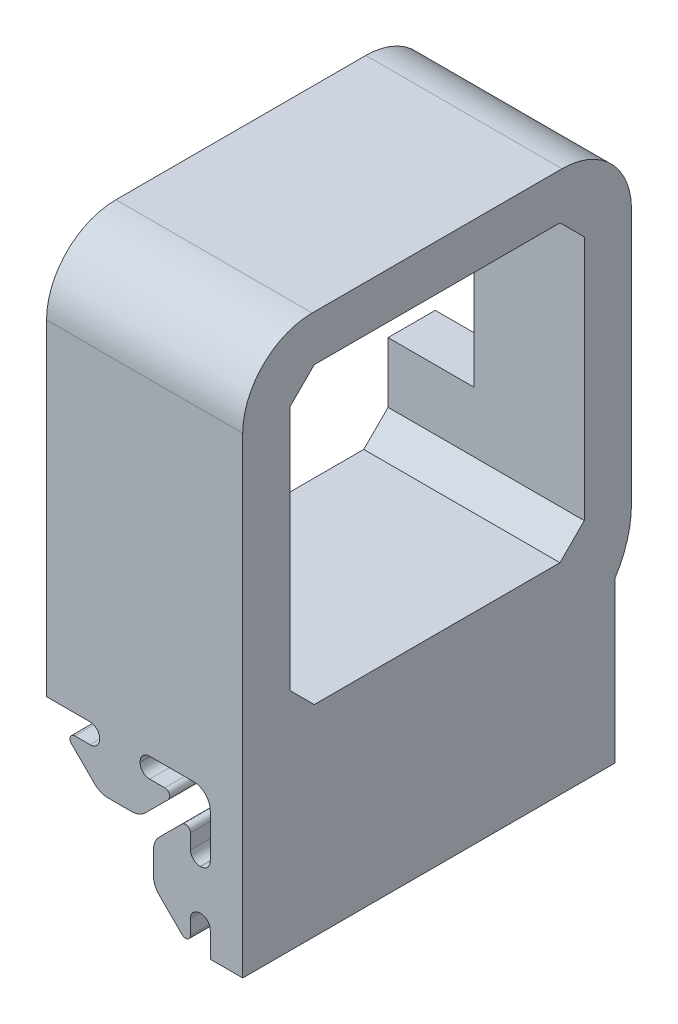
SolidWorks part; units mm, degrees
ref_plane "Front Plane" through (0, 0, 0) normal (0, 0, 1) x (1, 0, 0)
ref_plane "Top Plane" through (0, 0, 0) normal (0, 1, 0) x (1, 0, 0)
ref_plane "Right Plane" through (0, 0, 0) normal (1, 0, 0) x (0, 0, -1)
sketch "Sketch1" plane through (0, 0, 0) normal (0, 0, 1) x (1, 0, 0)
  line L0 (13.02, -7.9417) -> (17.7, -7.9417)
  line L1 (-10.5664, 13.02) -> (-10.5664, 70.02)
  line L2 (-10.5664, 70.02) -> (17.7, 70.02)
  line L3 (17.7, -7.9417) -> (17.7, 70.02)
  line L10 (12.7, -6.3331) -> (12.7, -7.9417) construction
  line L11 (13.02, -5.3171) -> (13.02, -4.2875)
  line L12 (11.651, -2.9185) -> (11.5392, -2.9185)
  line L13 (10.1702, -4.2875) -> (10.1702, -6.4021)
  line L14 (8.9631, -6.9029) -> (5.667, -3.6143)
  line L15 (4.8285, -1.5932) -> (4.8285, 1.5932)
  line L16 (5.667, 3.6143) -> (8.9631, 6.9029)
  line L17 (10.1702, 6.4021) -> (10.1702, 4.2875)
  line L18 (11.5392, 2.9185) -> (11.651, 2.9185)
  line L19 (13.02, 10.5773) -> (13.02, 4.2875)
  line L20 (6.3329, 13.02) -> (10.5626, 13.0198)
  line L22 (6.3329, 13.02) -> (4.2875, 13.02)
  line L23 (2.9185, 11.651) -> (2.9185, 11.5392)
  line L24 (4.2875, 10.1702) -> (6.4768, 10.1702)
  line L25 (6.981, 8.9509) -> (3.6723, 5.6497)
  line L26 (1.6558, 4.8158) -> (-1.6558, 4.8158)
  line L27 (-3.6723, 5.6497) -> (-6.981, 8.9509)
  line L28 (-6.4768, 10.1702) -> (-4.2875, 10.1702)
  line L29 (-2.9185, 11.5392) -> (-2.9185, 11.651)
  line L30 (-4.2875, 13.02) -> (-5.3171, 13.02)
  line L31 (-5.3171, 13.02) -> (-10.5664, 13.02)
  line L32 (13.02, -5.3171) -> (13.02, -7.9417)
  line L33 (13.02, -6.3331) -> (13.02, -7.9417) construction
  line L34 (13.02, 4.2875) -> (13.02, 5.3171) construction
  line L37 (5.3171, 13.02) -> (4.2875, 13.02) construction
  line L38 (-6.3331, 13.02) -> (-9.5504, 13.02) construction
  line L96 (12.7, -5.3171) -> (12.7, -4.2875) construction
  line L97 (11.651, -3.2385) -> (11.5392, -3.2385) construction
  line L98 (10.4902, -4.2875) -> (10.4902, -6.4021) construction
  line L99 (8.7371, -7.1294) -> (5.441, -3.8408) construction
  line L100 (4.5085, -1.5932) -> (4.5085, 1.5932) construction
  line L101 (5.441, 3.8408) -> (8.7371, 7.1294) construction
  line L102 (10.4902, 6.4021) -> (10.4902, 4.2875) construction
  line L103 (11.5392, 3.2385) -> (11.651, 3.2385) construction
  line L104 (12.7, 4.2875) -> (12.7, 5.3171) construction
  line L105 (12.7, 6.3331) -> (12.7, 9.5504) construction
  line L106 (9.5504, 12.7) -> (6.3331, 12.7) construction
  line L107 (5.3171, 12.7) -> (4.2875, 12.7) construction
  line L108 (3.2385, 11.651) -> (3.2385, 11.5392) construction
  line L109 (4.2875, 10.4902) -> (6.4768, 10.4902) construction
  line L110 (7.207, 8.7244) -> (3.8983, 5.4232) construction
  line L111 (1.6558, 4.4958) -> (-1.6558, 4.4958) construction
  line L112 (-3.8983, 5.4232) -> (-7.207, 8.7244) construction
  line L113 (-6.4768, 10.4902) -> (-4.2875, 10.4902) construction
  line L114 (-3.2385, 11.5392) -> (-3.2385, 11.651) construction
  line L115 (-4.2875, 12.7) -> (-5.3171, 12.7) construction
  line L116 (-6.3331, 12.7) -> (-9.5504, 12.7) construction
  arc A0 (13.02, -4.2875) -> (11.651, -2.9185) centre (11.651, -4.2875) ccw
  arc A1 (11.5392, -2.9185) -> (10.1702, -4.2875) centre (11.5392, -4.2875) ccw
  arc A2 (8.9631, -6.9029) -> (10.1702, -6.4021) centre (9.4628, -6.4021) ccw
  arc A3 (4.8285, -1.5932) -> (5.667, -3.6143) centre (7.6835, -1.5932) ccw
  arc A4 (5.667, 3.6143) -> (4.8285, 1.5932) centre (7.6835, 1.5932) ccw
  arc A5 (10.1702, 6.4021) -> (8.9631, 6.9029) centre (9.4628, 6.4021) ccw
  arc A6 (10.1702, 4.2875) -> (11.5392, 2.9185) centre (11.5392, 4.2875) ccw
  arc A7 (11.651, 2.9185) -> (13.02, 4.2875) centre (11.651, 4.2875) ccw
  arc A8 (4.2875, 13.02) -> (2.9185, 11.651) centre (4.2875, 11.651) ccw
  arc A9 (2.9185, 11.5392) -> (4.2875, 10.1702) centre (4.2875, 11.5392) ccw
  arc A10 (6.981, 8.9509) -> (6.4768, 10.1702) centre (6.4768, 9.4563) ccw
  arc A11 (1.6558, 4.8158) -> (3.6723, 5.6497) centre (1.6558, 7.6708) ccw
  arc A12 (-3.6723, 5.6497) -> (-1.6558, 4.8158) centre (-1.6558, 7.6708) ccw
  arc A13 (-6.4768, 10.1702) -> (-6.981, 8.9509) centre (-6.4768, 9.4563) ccw
  arc A14 (-4.2875, 10.1702) -> (-2.9185, 11.5392) centre (-4.2875, 11.5392) ccw
  arc A15 (-2.9185, 11.651) -> (-4.2875, 13.02) centre (-4.2875, 11.651) ccw
  arc A16 (13.02, 10.5773) -> (10.5626, 13.0198) centre (10.5918, 10.5918) ccw
  arc A17 (13.0198, 10.5625) -> (10.5626, 13.0198) centre (10.5918, 10.5918) ccw construction
  arc A114 (12.7, -5.3171) -> (12.7, -6.3331) centre (12.7, -5.8251) ccw construction
  arc A115 (12.7, -4.2875) -> (11.651, -3.2385) centre (11.651, -4.2875) ccw construction
  arc A116 (11.5392, -3.2385) -> (10.4902, -4.2875) centre (11.5392, -4.2875) ccw construction
  arc A117 (8.7371, -7.1294) -> (10.4902, -6.4021) centre (9.4628, -6.4021) ccw construction
  arc A118 (4.5085, -1.5932) -> (5.441, -3.8408) centre (7.6835, -1.5932) ccw construction
  arc A119 (5.441, 3.8408) -> (4.5085, 1.5932) centre (7.6835, 1.5932) ccw construction
  arc A120 (10.4902, 6.4021) -> (8.7371, 7.1294) centre (9.4628, 6.4021) ccw construction
  arc A121 (10.4902, 4.2875) -> (11.5392, 3.2385) centre (11.5392, 4.2875) ccw construction
  arc A122 (11.651, 3.2385) -> (12.7, 4.2875) centre (11.651, 4.2875) ccw construction
  arc A123 (12.7, 6.3331) -> (12.7, 5.3171) centre (12.7, 5.8251) ccw construction
  arc A124 (12.6998, 10.5664) -> (12.7, 9.5504) centre (12.7, 10.0584) ccw construction
  arc A125 (12.6998, 10.5664) -> (10.5664, 12.6998) centre (10.5918, 10.5918) ccw construction
  arc A126 (9.5504, 12.7) -> (10.5664, 12.6998) centre (10.0584, 12.7) ccw construction
  arc A127 (5.3171, 12.7) -> (6.3331, 12.7) centre (5.8251, 12.7) ccw construction
  arc A128 (4.2875, 12.7) -> (3.2385, 11.651) centre (4.2875, 11.651) ccw construction
  arc A129 (3.2385, 11.5392) -> (4.2875, 10.4902) centre (4.2875, 11.5392) ccw construction
  arc A130 (7.207, 8.7244) -> (6.4768, 10.4902) centre (6.4768, 9.4563) ccw construction
  arc A131 (1.6558, 4.4958) -> (3.8983, 5.4232) centre (1.6558, 7.6708) ccw construction
  arc A132 (-3.8983, 5.4232) -> (-1.6558, 4.4958) centre (-1.6558, 7.6708) ccw construction
  arc A133 (-6.4768, 10.4902) -> (-7.207, 8.7244) centre (-6.4768, 9.4563) ccw construction
  arc A134 (-4.2875, 10.4902) -> (-3.2385, 11.5392) centre (-4.2875, 11.5392) ccw construction
  arc A135 (-3.2385, 11.651) -> (-4.2875, 12.7) centre (-4.2875, 11.651) ccw construction
  arc A136 (-6.3331, 12.7) -> (-5.3171, 12.7) centre (-5.8251, 12.7) ccw construction
  arc A137 (-10.5664, 12.6998) -> (-9.5504, 12.7) centre (-10.0584, 12.7) ccw construction
  dimension "D1" = 57
  dimension "D6" = 5
  dimension "D8" = 0.32
  dimension "D7" = 6.2898
  dimension "D9" = 4.2297
extrude "Boss-Extrude1" add sketch "Sketch1" along normal blind 56 contours L3 L2 L1 L31 L30 A15 L29 A14 L28 A13 L27 A12 L26 A11 L25 A10 L24 A9 L23 A8 L22 L20 A16 L19 A7 L18 A6 L17 A5 L16 A4 L15 A3 L14 A2 L13 A1 L12 A0 L11 L32 L0
sketch "Sketch14" plane through (17.7, 0, 0) normal (1, 0, 0) x (0, 0, -1)
  line L4 (-56, -7.9417) -> (-56, 70.02) construction
  line L5 (0, -7.9417) -> (0, 70.02) construction
  line L6 (-56, 70.02) -> (0, 70.02) construction
  line L11 (0, 21.02) -> (-56, 21.02) construction
  line L12 (-28, 70.02) -> (-28, 21.02) construction
  line L14 (-49.2, 21.02) -> (-6.8, 21.02)
  line L15 (-49.2, 21.02) -> (-49.2, 63.42)
  line L16 (-49.2, 63.42) -> (-6.8, 63.42)
  line L17 (-6.8, 21.02) -> (-6.8, 63.42)
  point P14 (-28, 63.42)
  dimension "D1" = 42.4
  dimension "D2" = 42.4
  dimension "D3" = 6.6
other "AlignGroup1"
extrude "Cut-Extrude1" cut sketch "Sketch14" against normal blind 56
chamfer "Chamfer1" distance 3.5 4 edges at (3.5668, 21.02, 6.8) (3.5668, 21.02, 49.2) (3.5668, 63.42, 6.8) (3.5668, 63.42, 49.2)
fillet "Fillet1" radius 10 2 edges at (3.5668, 70.02, 56) (3.5668, 70.02, 0)
sketch "Sketch16" plane through (17.7, 0, 0) normal (1, 0, 0) x (0, 0, -1)
  line L1 (-56, -7.9417) -> (-53.6, -7.9417)
  line L2 (-56, -7.9417) -> (-56, 15.0583)
  line L3 (-56, 15.0583) -> (-53.6, 15.0583)
  line L4 (-53.6, -7.9417) -> (-53.6, 15.0583)
  dimension "D1" = 23
  dimension "D2" = 2.4
extrude "Cut-Extrude3" cut sketch "Sketch16" against normal through all
sketch "Sketch17" plane through (0, 0, 56) normal (0, 0, 1) x (1, 0, 0)
  line L0 (17.7, 42.22) -> (-10.5664, 42.22) construction
  line L2 (-13.62, 51.22) -> (1.8336, 51.22)
  line L3 (-13.62, 51.22) -> (-13.62, 33.22)
  line L4 (17.7, 24.52) -> (17.7, 59.92)
  line L5 (-10.5664, 24.52) -> (17.7, 24.52)
  line L6 (-10.5664, 59.92) -> (-10.5664, 24.52)
  line L7 (17.7, 59.92) -> (-10.5664, 59.92)
  line L8 (17.7, 24.52) -> (17.7, 59.92) construction
  line L9 (-10.5664, 24.52) -> (17.7, 24.52) construction
  line L10 (-10.5664, 59.92) -> (-10.5664, 24.52) construction
  line L12 (-13.62, 33.22) -> (1.8336, 33.22)
  line L13 (1.8336, 51.22) -> (1.8336, 33.22)
  point P10 (1.8336, 42.22)
  dimension "D2" = 18
  dimension "D3" = 12.4
  dimension "D1" = 0
extrude "Cut-Extrude4" cut sketch "Sketch17" against normal up to next
fillet "Fillet4" radius 15 1 edges at (3.5668, 15.0583, 56)
mirror "Mirror2" about plane through (-4.2875, 11.651, 0) normal (0, 0, 1) of bodies 126
sketch "Sketch18" plane through (0, 0, 0) normal (0, 0, -1) x (-1, 0, 0)
  line L0 (-23.6085, 16.9143) -> (-37.3681, 16.9143)
  line L1 (-23.6085, 487.7984) -> (16.3915, 487.7984)
  line L2 (-23.6085, 487.7984) -> (-23.6085, 16.9143)
  line L3 (-23.6085, -12.2016) -> (16.3915, -12.2016)
  line L4 (16.3915, 487.7984) -> (16.3915, -12.2016)
  line L5 (-37.3681, 16.9143) -> (-37.3681, -12.2016)
  line L6 (-37.3681, -12.2016) -> (-23.6085, -12.2016)
  dimension "D1" = 500
  dimension "D2" = 40
extrude "Cut-Extrude5" cut sketch "Sketch18" against normal through all
